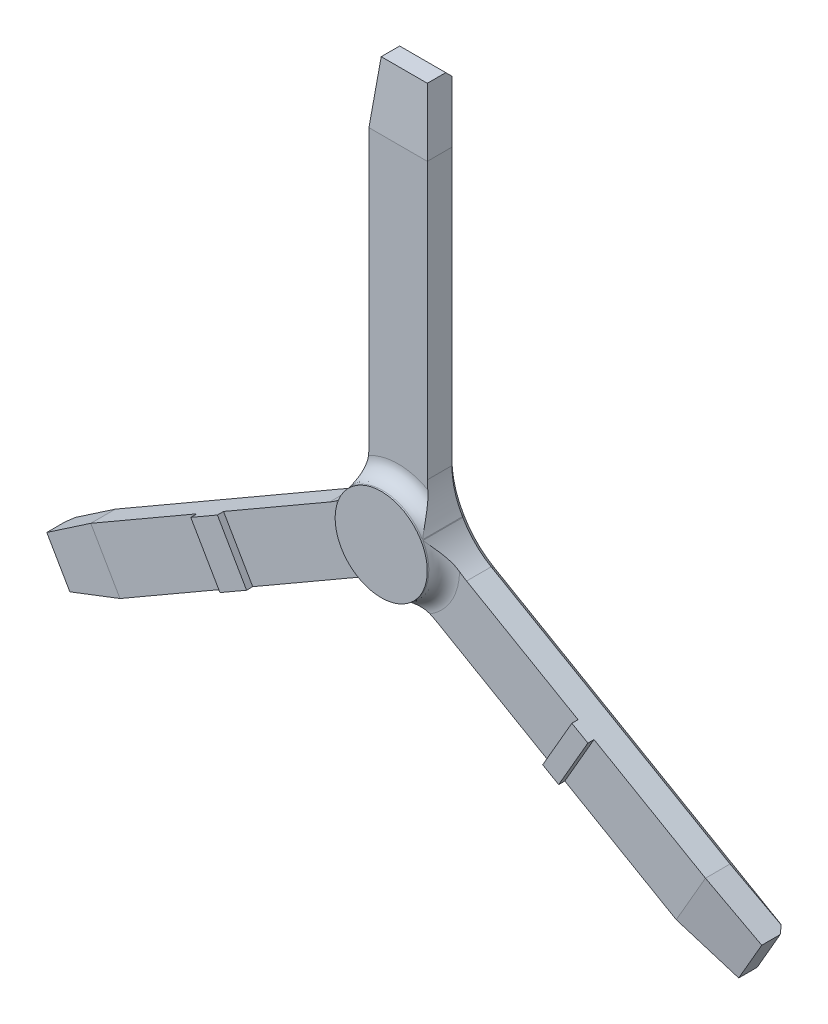
SolidWorks part; units mm, degrees
ref_plane "Front Plane" through (0, 0, 0) normal (0, 0, 1) x (1, 0, 0)
ref_plane "Top Plane" through (0, 0, 0) normal (0, 1, 0) x (1, 0, 0)
ref_plane "Right Plane" through (0, 0, 0) normal (1, 0, 0) x (0, 0, -1)
sketch "Sketch1" plane through (0, 0, 0) normal (0, 0, 1) x (1, 0, 0)
  line L0 (-1.9, 24) -> (1.9, 24) construction
  line L1 (0, 0) -> (0, 24) construction
  line L2 (-1.9, 24) -> (-1.9, 26)
  line L3 (-1.9, 26) -> (1.9, 26)
  line L4 (1.9, 26) -> (1.9, 24)
  line L5 (23.4667, -11.3546) -> (21.5667, -14.6454)
  line L6 (21.5667, -14.6454) -> (19.8346, -13.6454)
  line L7 (21.7346, -10.3546) -> (23.4667, -11.3546)
  line L8 (-21.5667, -14.6454) -> (-23.4667, -11.3546)
  line L9 (-23.4667, -11.3546) -> (-21.7346, -10.3546)
  line L10 (-19.8346, -13.6454) -> (-21.5667, -14.6454)
  line L11 (0, 0) -> (1.9, 24) construction
  line L12 (0, 0) -> (19.8346, -13.6454) construction
  line L13 (-1.9, 24) -> (-1.9, 1.097)
  line L14 (-1.9, 1.097) -> (-21.7346, -10.3546)
  line L15 (-19.8346, -13.6454) -> (0, -2.1939)
  line L16 (0, -2.1939) -> (19.8346, -13.6454)
  line L17 (21.7346, -10.3546) -> (1.9, 1.097)
  line L18 (1.9, 1.097) -> (1.9, 24)
  circle A0 centre (0, 0) radius 24 construction
  dimension "D1" = 48
  dimension "D2" = 3.8
  dimension "D3" = 2
  dimension "D4" = 120
  dimension "D5" = 24.0751
  dimension "D6" = 3
extrude "Boss-Extrude1" add sketch "Sketch1" along normal blind 2 contours L18 A0 L13 L14 L15 L16 L17 region at (0, 0, 0)
chamfer "Chamfer1" distance 4 distance2 0.4 3 edges at (22.5167, -13, 2) (-22.5167, -13, 2) (0, 26, 2) first distance on face at (0, 0, 2)
chamfer "Chamfer2" distance 0.4 distance2 4 3 edges at (23.4667, -11.3546, 0.8) (-1.9, 26, 0.8) (-21.5667, -14.6454, 0.8) first distance on face at (22.5167, -13, 0.8) first distance on face at (0, 26, 0.8) first distance on face at (-22.5167, -13, 0.8)
chamfer "Chamfer3" distance 4 distance2 0.4 3 edges at (1.9, 26, 0.8) (21.5667, -14.6454, 0.8) (-23.4667, -11.3546, 0.8) first distance on face at (1.9, 15.2388, 1.12) first distance on face at (12.2472, -9.2648, 1.12) first distance on face at (-14.1472, -5.9739, 1.12)
sketch "Sketch2" plane through (0, 0, 0) normal (0, 0, -1) x (-1, 0, 0)
  circle A0 centre (0, 0) radius 3
  dimension "D1" = 6
extrude "Boss-Extrude2" add sketch "Sketch2" against normal blind 3.1
fillet "Fillet1" radius 5 6 edges at (1.9, 2.3216, 1) (2.9606, 0.4846, 1) (1.0606, -2.8063, 1) (-1.0606, -2.8063, 1) (-2.9606, 0.4846, 1) (-1.9, 2.3216, 1)
fillet "Fillet2" radius 1 3 edges at (0, 3, 2) (2.5981, -1.5, 2) (-2.5981, -1.5, 2)
chamfer "Chamfer4" distance 0.4 angle 45 18 edges at (22.5167, -13, 0) (-22.5167, -13, 0) (0, 26, 0) (12.2293, -4.8667, 0) (3.4082, 0.4282, 0) (2.5981, 1.5, 0) (2.0749, 2.7374, 0) (1.9, 13.0242, 0) (-12.2293, -4.8667, 0) (-3.4082, 0.4282, 0) (-2.5981, 1.5, 0) (-2.0749, 2.7374, 0) (-1.9, 13.0242, 0) (10.3293, -8.1576, 0) (1.3332, -3.1657, 0) (0, -3, 0) (-1.3332, -3.1657, 0) (-10.3293, -8.1576, 0)
sketch "Sketch3" plane through (0, 0, 2) normal (0, 0, 1) x (1, 0, 0)
  line L0 (-12.2293, -4.8667) -> (-10.3293, -8.1576) construction
  line L1 (-4.4561, -0.3788) -> (-20.0026, -9.3546) construction
  line L2 (-2.5561, -3.6697) -> (-18.1026, -12.6454) construction
  line L3 (-13.0953, -5.3667) -> (-11.1953, -8.6576)
  line L4 (2.5561, -3.6697) -> (18.1026, -12.6454) construction
  line L5 (10.3293, -8.1576) -> (12.2293, -4.8667) construction
  line L6 (20.0026, -9.3546) -> (4.4561, -0.3788) construction
  line L7 (-13.0953, -5.3667) -> (-11.3633, -4.3667)
  line L8 (-11.1953, -8.6576) -> (-9.4633, -7.6576)
  line L9 (-11.3633, -4.3667) -> (-9.4633, -7.6576)
  line L10 (-13.0953, -5.3667) -> (-9.4633, -7.6576) construction
  line L11 (-11.1953, -8.6576) -> (-11.3633, -4.3667) construction
  line L12 (11.7097, -4.5667) -> (9.8097, -7.8576)
  line L13 (11.7097, -4.5667) -> (12.7489, -5.1667)
  line L14 (9.8097, -7.8576) -> (10.8489, -8.4576)
  line L15 (12.7489, -5.1667) -> (10.8489, -8.4576)
  line L16 (11.7097, -4.5667) -> (10.8489, -8.4576) construction
  line L17 (9.8097, -7.8576) -> (12.7489, -5.1667) construction
  point P13 (-11.2793, -6.5121)
  point P14 (11.2793, -6.5121)
  dimension "D1" = 2
  dimension "D2" = 1.2
extrude "Boss-Extrude3" add sketch "Sketch3" along normal blind 0.4
